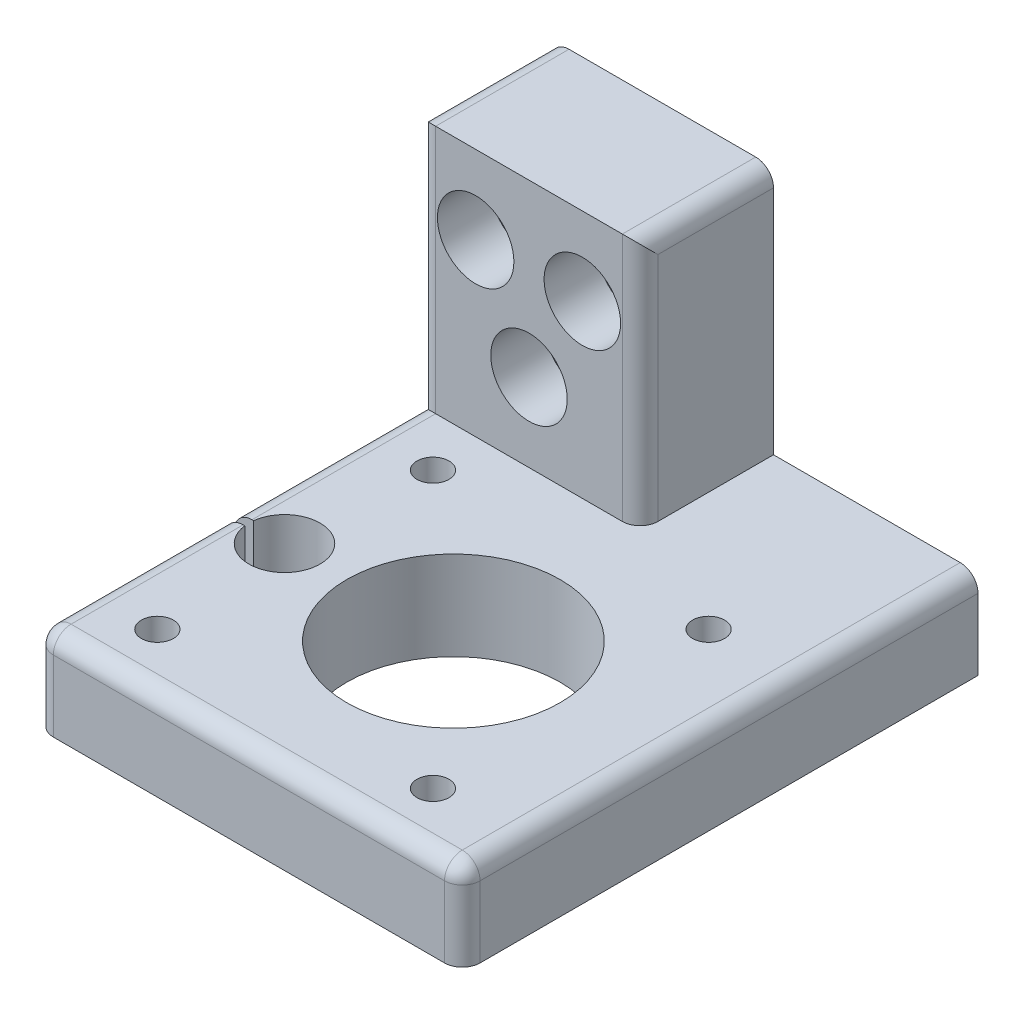
SolidWorks part; units mm, degrees
ref_plane "Front Plane" through (0, 0, 0) normal (0, 0, 1) x (1, 0, 0)
ref_plane "Top Plane" through (0, 0, 0) normal (0, 1, 0) x (1, 0, 0)
ref_plane "Right Plane" through (0, 0, 0) normal (1, 0, 0) x (0, 0, -1)
sketch "Sketch1" plane through (0, 0, 0) normal (0, 1, 0) x (1, 0, 0)
  line L0 (7.35, -20.65) -> (38.35, -20.65) construction
  line L1 (0, 0) -> (48, 0)
  line L2 (0, 0) -> (0, -58)
  line L3 (0, -58) -> (48, -58)
  line L4 (48, 0) -> (48, -58)
  line L5 (38.35, -20.65) -> (38.35, -51.65) construction
  line L6 (38.35, -51.65) -> (7.35, -51.65) construction
  line L7 (7.35, -51.65) -> (7.35, -20.65) construction
  line L8 (25.15, -36.15) -> (6.15, -36.15) construction
  line L9 (6.15, -36.15) -> (0, -36.15) construction
  line L11 (0, -35.65) -> (2.1814, -35.65)
  line L12 (0, -35.65) -> (0, -36.65)
  line L13 (0, -36.65) -> (2.1814, -36.65)
  line L14 (2.1814, -35.65) -> (2.1814, -36.65)
  circle A0 centre (7.35, -20.65) radius 1.8
  circle A1 centre (38.35, -20.65) radius 1.8
  circle A2 centre (38.35, -51.65) radius 1.8
  circle A3 centre (7.35, -51.65) radius 1.8
  circle A4 centre (25.15, -36.15) radius 12
  circle A5 centre (6.15, -36.15) radius 4
  dimension "D3" = 31
  dimension "D4" = 3.6
  dimension "D7" = 8
  dimension "D8" = 24
  dimension "D1" = 58
  dimension "D2" = 48
  dimension "D5" = 6.35
  dimension "D6" = 7.35
  dimension "D9" = 22.85
  dimension "D10" = 21.85
  dimension "D11" = 19
  dimension "D12" = 1
extrude "Boss-Extrude1" add sketch "Sketch1" along normal blind 10 contours A5 L11 L4 L1 L2 L3 L13 A4 A3 A2 A1 A0 region at (24, 0, 0.7529)
sketch "Sketch2" plane through (0, 0, 0) normal (1, 0, 0) x (0, 0, -1)
  line L1 (0, 10) -> (-15, 10)
  line L2 (0, 10) -> (0, 38)
  line L3 (0, 38) -> (-15, 38)
  line L4 (-15, 10) -> (-15, 38)
  dimension "D1" = 28
  dimension "D2" = 15
extrude "Boss-Extrude2" add sketch "Sketch2" along normal blind 25
sketch "Sketch3" plane through (0, 0, 15) normal (0, 0, 1) x (1, 0, 0)
  line L0 (6.5, 29.1962) -> (18.5, 29.1962) construction
  line L1 (18.5, 29.1962) -> (12.5, 18.8038) construction
  line L2 (12.5, 18.8038) -> (6.5, 29.1962) construction
  line L3 (12.5, 18.8038) -> (12.5, 10) construction
  line L4 (25, 10) -> (0, 10) construction
  line L5 (12.5, 29.1962) -> (12.5, 38) construction
  line L6 (25, 38) -> (0, 38) construction
  circle A0 centre (6.5, 29.1962) radius 2.8
  circle A1 centre (18.5, 29.1962) radius 2.8
  circle A2 centre (12.5, 18.8038) radius 2.8
  dimension "D1" = 12
  dimension "D2" = 5.6
extrude "Cut-Extrude1" cut sketch "Sketch3" against normal through all
sketch "Sketch4" plane through (0, 0, 15) normal (0, 0, 1) x (1, 0, 0)
  circle A0 centre (6.5, 29.1962) radius 4.3
  circle A1 centre (18.5, 29.1962) radius 4.3
  circle A2 centre (12.5, 18.8038) radius 4.3
  dimension "D1" = 8.6
extrude "Cut-Extrude2" cut sketch "Sketch4" against normal blind 6
fillet "Fillet1" radius 2 10 edges at (48, 5, 58) (0, 5, 58) (0, 10, 47.325) (24, 10, 58) (48, 10, 29) (0, 24, 15) (0, 38, 7.5) (25, 24, 15) (25, 38, 7.5) (0, 10, 25.325)
